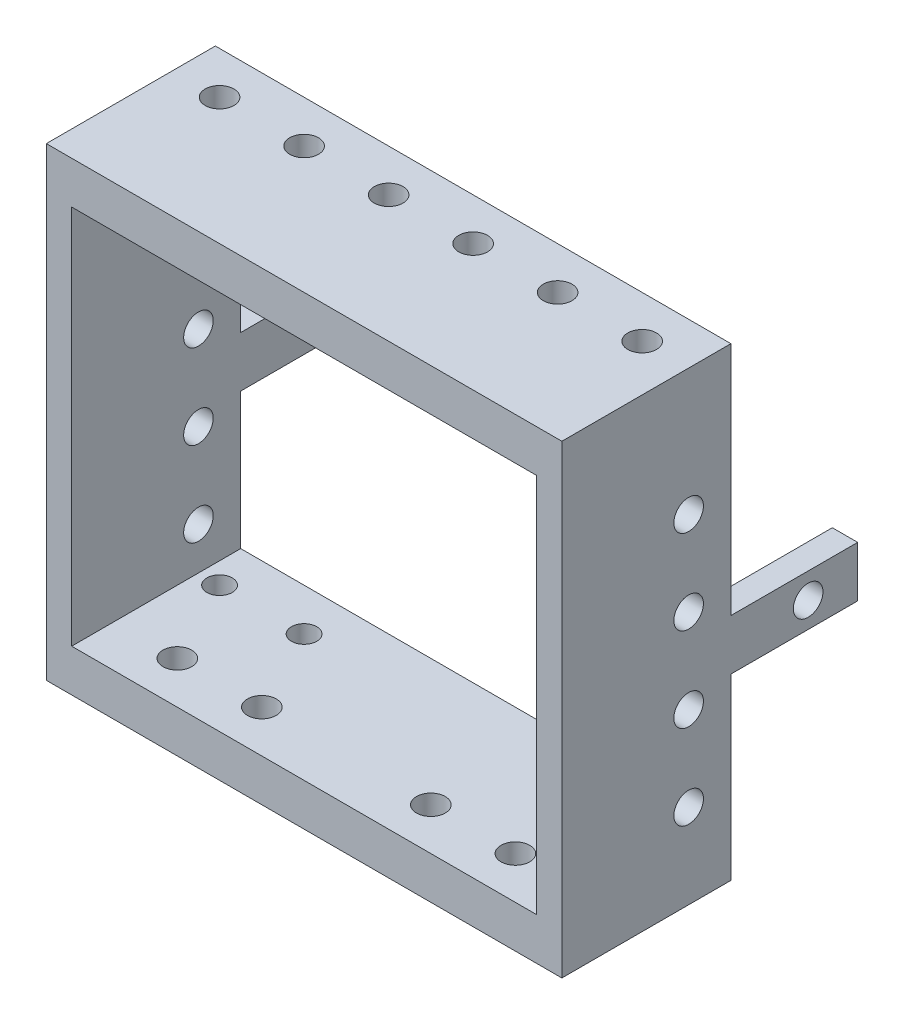
SolidWorks part; units mm, degrees
ref_plane "Front Plane" through (0, 0, 0) normal (0, 0, 1) x (1, 0, 0)
ref_plane "Top Plane" through (0, 0, 0) normal (0, 1, 0) x (1, 0, 0)
ref_plane "Right Plane" through (0, 0, 0) normal (1, 0, 0) x (0, 0, -1)
sketch "Sketch1" plane through (0, 0, 0) normal (0, 1, 0) x (1, 0, 0)
  line L1 (-23.3554, -4.3957) -> (37.6446, -4.3957)
  line L2 (-23.3554, -4.3957) -> (-23.3554, 5.6043)
  line L3 (-23.3554, 5.6043) -> (37.6446, 5.6043)
  line L4 (37.6446, -4.3957) -> (37.6446, 5.6043)
  circle A0 centre (-17.8554, 0.6043) radius 1.5
  circle A1 centre (-7.8554, 0.6043) radius 1.5
  circle A2 centre (22.1446, 0.6043) radius 1.5
  circle A3 centre (32.1446, 0.6043) radius 1.5
  dimension "D5" = 3
  dimension "D1" = 10
  dimension "D2" = 10
  dimension "D3" = 5.5
  dimension "D4" = 5.5
  dimension "D6" = 10
  dimension "D7" = 30
  dimension "D8" = 5
extrude "Boss-Extrude1" add sketch "Sketch1" along normal blind 5
sketch "Sketch2" plane through (0, 5, 0) normal (0, 1, 0) x (1, 0, 0)
  line L0 (37.6446, -4.3957) -> (37.6446, 5.6043) construction
  line L1 (-23.3554, -4.3957) -> (37.6446, -4.3957) construction
  line L2 (-23.3554, 5.6043) -> (-23.3554, -4.3957) construction
  line L3 (37.6446, 5.6043) -> (-23.3554, 5.6043) construction
  line L4 (37.6446, -4.3957) -> (37.6446, 5.6043)
  line L5 (-23.3554, -4.3957) -> (-20.3554, -4.3957)
  line L6 (-23.3554, 5.6043) -> (-23.3554, -4.3957)
  line L7 (37.6446, 5.6043) -> (34.6446, 5.6043)
  line L8 (-20.3554, 5.6043) -> (-20.3554, -4.3957)
  line L9 (34.6446, 5.6043) -> (34.6446, -4.3957)
  line L10 (-20.3554, 5.6043) -> (-23.3554, 5.6043)
  line L11 (34.6446, -4.3957) -> (37.6446, -4.3957)
  dimension "D1" = 3
  dimension "D2" = 3
extrude "Boss-Extrude2" add sketch "Sketch2" along normal blind 45
sketch "Sketch3" plane through (-23.3554, 0, 0) normal (-1, 0, 0) x (0, 0, 1)
  line L0 (-5.6043, 5) -> (4.3957, 5) construction
  line L1 (-5.6043, 5) -> (4.3957, 5) construction
  line L2 (-5.6043, 50) -> (-5.6043, 0) construction
  circle A0 centre (-0.6043, 10) radius 1.75
  dimension "D1" = 3.5
  dimension "D2" = 5
  dimension "D3" = 5
extrude "Cut-Extrude1" cut sketch "Sketch3" against normal through all contours A0
sketch "Sketch4" plane through (-23.3554, 0, 0) normal (-1, 0, 0) x (0, 0, 1)
  line L0 (-5.6043, 50) -> (-5.6043, 0) construction
  line L1 (-5.6043, 21.14) -> (-20.6043, 21.14)
  line L2 (-5.6043, 21.14) -> (-5.6043, 27.14)
  line L3 (-5.6043, 27.14) -> (-20.6043, 27.14)
  line L4 (-20.6043, 21.14) -> (-20.6043, 27.14)
  circle A0 centre (-14.7443, 24.14) radius 1.75
  circle A1 centre (-0.6043, 10) radius 1.75 construction
  dimension "D1" = 3.5
  dimension "D3" = 14.14
  dimension "D5" = 3
  dimension "D2" = 14.14
  dimension "D4" = 6
  dimension "D6" = 15
extrude "Boss-Extrude3" add sketch "Sketch4" against normal blind 3 contours L1 L4 L3 L2
ref_plane "Plane1" through (7.1446, 0, 0) normal (-1, 0, 0) x (0, 0, 1)
mirror "Mirror1" about plane through (7.1446, 0, 0) normal (-1, 0, 0) of "Boss-Extrude3"
sketch "Sketch5" plane through (-23.3554, 0, 0) normal (-1, 0, 0) x (0, 0, 1)
  circle A0 centre (-14.7443, 24.14) radius 1.75
  circle A1 centre (-0.6043, 10) radius 1.75 construction
  dimension "D1" = 3.5
  dimension "D2" = 14.14
  dimension "D3" = 14.14
extrude "Cut-Extrude2" cut sketch "Sketch5" against normal through all
sketch "Sketch6" plane through (0, 50, 0) normal (0, 1, 0) x (1, 0, 0)
  line L0 (7.1446, 13.75) -> (7.1446, -13.75) construction
  line L1 (-23.3554, -4.3957) -> (37.6446, -4.3957)
  line L2 (-23.3554, -4.3957) -> (-23.3554, 5.6043)
  line L3 (-23.3554, 5.6043) -> (37.6446, 5.6043)
  line L4 (37.6446, -4.3957) -> (37.6446, 5.6043)
  circle A0 centre (2.1446, 0.6043) radius 1.7
  circle A1 centre (12.1446, 0.6043) radius 1.7
  circle A2 centre (-7.8554, 0.6043) radius 1.7
  circle A3 centre (-17.8554, 0.6043) radius 1.7
  circle A4 centre (22.1446, 0.6043) radius 1.7
  circle A5 centre (32.1446, 0.6043) radius 1.7
  dimension "D1" = 3.4
  dimension "D2" = 5
  dimension "D3" = 5
  dimension "D4" = 3
  dimension "D5" = 3
extrude "Boss-Extrude4" add sketch "Sketch6" along normal blind 5
sketch "Sketch7" plane through (-23.3554, 0, 0) normal (-1, 0, 0) x (0, 0, 1)
  circle A0 centre (-0.6043, 10) radius 1.75 construction
  circle A1 centre (-0.6043, 10) radius 1.75
  circle A2 centre (-0.6043, 20) radius 1.75
  circle A3 centre (-0.6043, 30) radius 1.75
  circle A4 centre (-0.6043, 40) radius 1.75
  circle A6 centre (-0.6043, 50) radius 1.75 [skipped]
  dimension "D1" = 5
extrude "Cut-Extrude3" cut sketch "Sketch7" against normal through all
sketch "Sketch8" plane through (0, 0, 4.3957) normal (0, 0, 1) x (1, 0, 0)
  line L0 (37.6446, 55) -> (37.6446, 0) construction
  line L1 (-20.3554, 50) -> (34.6446, 50)
  line L2 (-20.3554, 50) -> (-20.3554, 5)
  line L3 (-20.3554, 5) -> (34.6446, 5)
  line L4 (34.6446, 50) -> (34.6446, 5)
  line L5 (-23.3554, 55) -> (37.6446, 55)
  line L6 (-23.3554, 55) -> (-23.3554, 0)
  line L7 (-23.3554, 0) -> (37.6446, 0)
  line L8 (37.6446, 55) -> (37.6446, 0)
extrude "Boss-Extrude5" add sketch "Sketch8" along normal blind 10
sketch "Sketch13" plane through (0, 0, 0) normal (0, -1, 0) x (1, 0, 0)
  line L0 (7.1446, 19.25) -> (7.1446, -19.25) construction
  line L1 (-23.3554, 14.3957) -> (37.6446, 14.3957) construction
  circle A0 centre (-2.8554, 9.3957) radius 1.7
  circle A1 centre (-12.8554, 9.3957) radius 1.7
  circle A2 centre (17.1446, 9.3957) radius 1.7
  circle A3 centre (27.1446, 9.3957) radius 1.7
  dimension "D1" = 3.4
  dimension "D2" = 10
  dimension "D3" = 10
  dimension "D4" = 5
extrude "Cut-Extrude5" cut sketch "Sketch13" against normal blind 18
